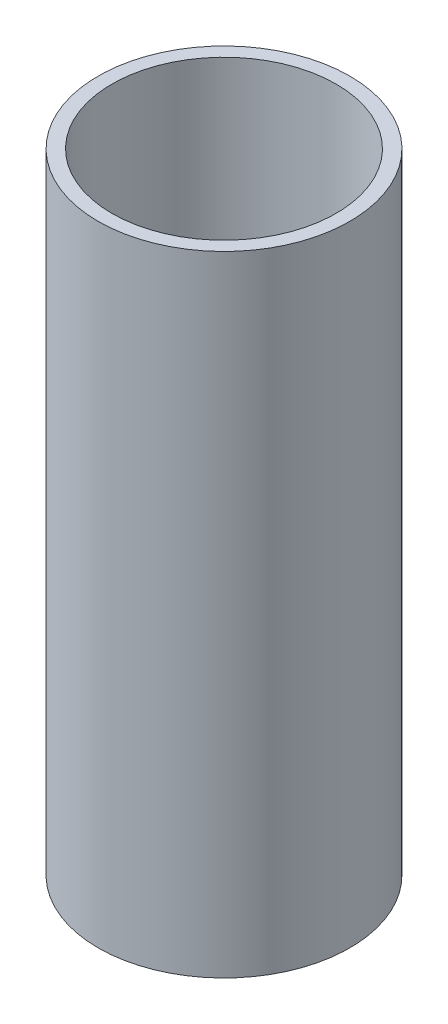
SolidWorks part; units mm, degrees
ref_plane "Front Plane" through (0, 0, 0) normal (0, 0, 1) x (1, 0, 0)
ref_plane "Top Plane" through (0, 0, 0) normal (0, 1, 0) x (1, 0, 0)
ref_plane "Right Plane" through (0, 0, 0) normal (1, 0, 0) x (0, 0, -1)
sketch "Sketch1" plane through (0, 0, 0) normal (0, 1, 0) x (1, 0, 0)
  circle A0 centre (0, 0) radius 14.25
  circle A1 centre (0, 0) radius 16
  dimension "D1" = 28.5
  dimension "D2" = 32
extrude "Boss-Extrude1" add sketch "Sketch1" along normal blind 80
